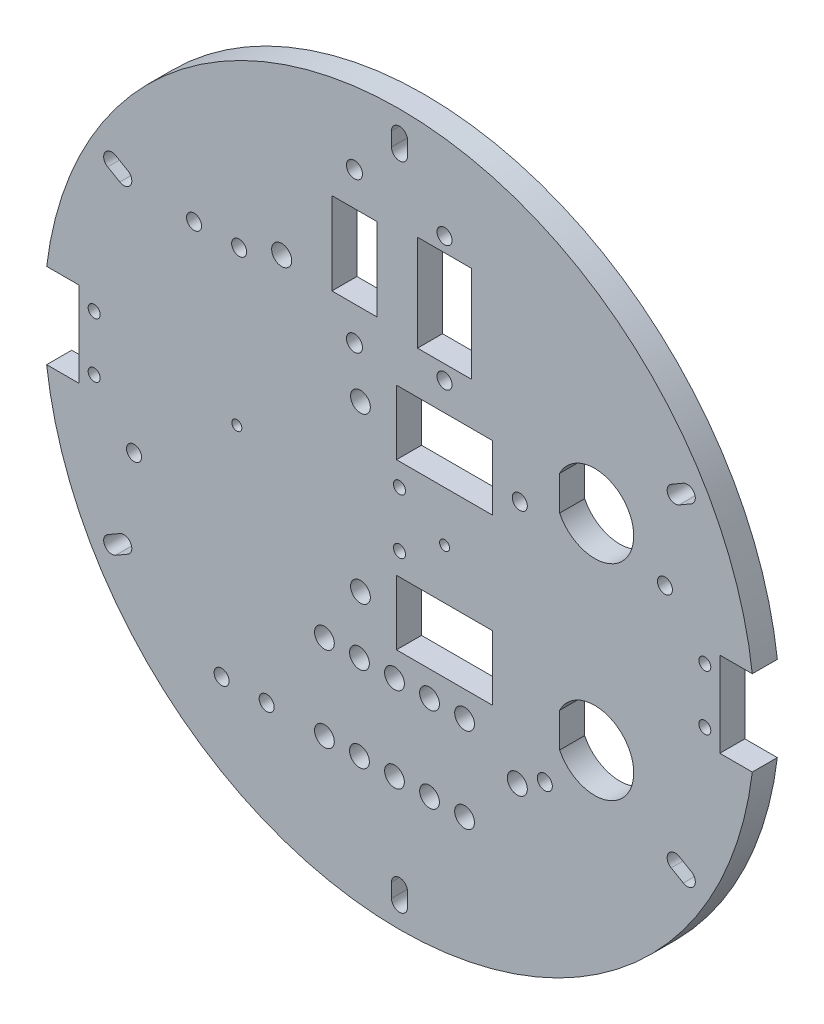
SolidWorks part; units mm, degrees
material "Alliage 1060"
ref_plane "Plan de face" through (0, 0, 0) normal (0, 0, 1) x (1, 0, 0)
ref_plane "Plan de dessus" through (0, 0, 0) normal (0, 1, 0) x (1, 0, 0)
ref_plane "Plan de droite" through (0, 0, 0) normal (1, 0, 0) x (0, 0, -1)
sketch "Esquisse1" plane through (0, 0, 0) normal (0, 0, 1) x (1, 0, 0)
  circle A0 centre (0, 0) radius 71
  dimension "D1" = 142
extrude "Boss.-Extru.1" add sketch "Esquisse1" along normal blind 5
sketch "Esquisse2" plane through (0, 0, 5) normal (0, 0, 1) x (1, 0, 0)
  line L0 (0, 0) -> (0, -76.1453) construction
  line L1 (97.9923, -8.5) -> (64, -8.5)
  line L2 (97.9923, -8.5) -> (97.9923, 8.5)
  line L3 (97.9923, 8.5) -> (64, 8.5)
  line L4 (64, -8.5) -> (64, 8.5)
  line L5 (0, 0) -> (103.2685, 0) construction
  line L7 (-85.8614, -8.5) -> (-64, -8.5)
  line L8 (-85.8614, -8.5) -> (-85.8614, 8.5)
  line L9 (-85.8614, 8.5) -> (-64, 8.5)
  line L10 (-64, -8.5) -> (-64, 8.5)
  dimension "D1" = 128
  dimension "D2" = 17
extrude "Enlèv. mat.-Extru.1" cut sketch "Esquisse2" against normal through all
hole_wizard "Dégagement M21" positions "Esquisse3" profile "Esquisse4" hole size "M2" standard "ISO" end condition through all
sketch "Esquisse3" plane through (0, 0, 0) normal (0, 0, -1) x (-1, 0, 0)
  line L0 (-64, 8.5) -> (-64, -8.5) construction
  line L1 (-64, 0) -> (-80.7851, 0) construction
  point P0 (-61, -5.5)
  dimension "D1" = 3
  dimension "D2" = 5.5
sketch "Esquisse4" plane through (61, -5.5, 0) normal (1, 0, 0) x (0, 1, 0)
  line L0 (0, 0) -> (0, 5)
  line L1 (0, 5) -> (1.2, 5)
  line L2 (1.2, 5) -> (1.2, 0)
  line L5 (1.2, 0) -> (0, 0)
  line L11 (0, -6.35) -> (0, 107.95) construction
  dimension "Diamètre du perçage jusqu'au prochain" = 2.4
  dimension "Profondeur du perçage jusqu'au prochain" = 5
pattern_linear "Répétition linéaire1" count 3 spacing 61 along (-1, 0, 0) count 2 spacing 11 along (0, 1, 0) of "Dégagement M21"
sketch "Esquisse7" plane through (0, 0, 0) normal (0, 0, -1) x (-1, 0, 0)
  line L1 (0, 0) -> (32.5, 0) construction
  circle A0 centre (32.5, 0) radius 1
  dimension "D2" = 2
  dimension "D4" = 32.5
extrude "Enlèv. mat.-Extru.2" cut sketch "Esquisse7" against normal blind 10
sketch "Esquisse8" plane through (0, 0, 5) normal (0, 0, 1) x (1, 0, 0)
  line L0 (32, 23.9409) -> (32, 17.0591)
  line L1 (64, 8.5) -> (64, -8.5) construction
  line L2 (70.4894, 8.5) -> (64, 8.5) construction
  line L3 (64, 0) -> (28.4808, 0) construction
  line L4 (32, -23.9409) -> (32, -17.0591)
  arc A0 (32, 23.9409) -> (32, 17.0591) centre (39, 20.5) cw
  arc A1 (32, -23.9409) -> (32, -17.0591) centre (39, -20.5) ccw
  point P5 (46.8, 20.5)
  dimension "D1" = 7.8
  dimension "D2" = 14.8
  dimension "D3" = 25
  dimension "D4" = 12
extrude "Enlèv. mat.-Extru.3" cut sketch "Esquisse8" against normal through all
hole_wizard "Dégagement M25" positions "Esquisse9" profile "Esquisse10" size "M2" standard "ISO" slot yes end condition through all
sketch "Esquisse9" plane through (0, 0, 5) normal (0, 0, 1) x (1, 0, 0)
  line L0 (0, 0) -> (56.2917, -32.5) construction
  line L2 (0, 0) -> (69.2789, 0) construction
  line L3 (53.6936, -31) -> (58.8897, -34) construction
  point P0 (56.2917, -32.5)
  dimension "D1" = 65
  dimension "D2" = 30
  dimension "D3" = 6
sketch "Esquisse10" plane through (56.2917, -32.5, 5) normal (1, 0, 0) x (0, -1, 0)
  line L0 (0, 0) -> (0, 5)
  line L1 (0, 5) -> (1.6, 5)
  line L2 (1.6, 5) -> (1.6, 0)
  line L5 (1.6, 0) -> (0, 0)
  line L11 (0, -6.35) -> (0, 107.95) construction
  dimension "Diamètre du perçage jusqu'au prochain" = 3.2
  dimension "Profondeur du perçage jusqu'au prochain" = 5
pattern_circular "Répétition circulaire1" count 6 over 360 about axis through (0, 0, 0) along (0, 0, 1) of "Dégagement M25"
sketch "Esquisse11" plane through (0, 0, 0) normal (0, 0, -1) x (-1, 0, 0)
  line L0 (0, 0) -> (-45.0649, 0) construction
  line L1 (-18.6, -10) -> (0.6, -10)
  line L2 (-18.6, -10) -> (-18.6, -22.9)
  line L3 (-18.6, -22.9) -> (0.6, -22.9)
  line L4 (0.6, -10) -> (0.6, -22.9)
  line L5 (0.6, 10) -> (0.6, 22.9)
  line L6 (-18.6, 22.9) -> (0.6, 22.9)
  line L7 (-18.6, 10) -> (-18.6, 22.9)
  line L8 (-18.6, 10) -> (0.6, 10)
  line L9 (22.5124, 41) -> (-32.2474, 41) construction
  line L10 (13.5, 32.75) -> (4.5, 32.75)
  line L11 (13.5, 32.75) -> (13.5, 49.25)
  line L12 (13.5, 49.25) -> (4.5, 49.25)
  line L13 (4.5, 32.75) -> (4.5, 49.25)
  line L14 (9, 56) -> (9, 26) construction
  line L15 (-9, 53.5) -> (-9, 28.5) construction
  line L16 (-18.6, 10) -> (0.6, -10) construction
  line L17 (-14.4, 50.6) -> (-3.6, 50.6)
  line L18 (-14.4, 50.6) -> (-14.4, 31.4)
  line L19 (-14.4, 31.4) -> (-3.6, 31.4)
  line L20 (-3.6, 50.6) -> (-3.6, 31.4)
  line L21 (0.6, 10) -> (-18.6, -10) construction
  circle A0 centre (9, 26) radius 1.6
  circle A1 centre (9, 56) radius 1.6
  circle A2 centre (-9, 28.5) radius 1.5
  circle A3 centre (-9, 53.5) radius 1.5
  circle A4 centre (7.8, 16.45) radius 1.975
  circle A5 centre (7.8, -16.45) radius 1.975
  circle A6 centre (-9, 0) radius 1
  point P27 (4.5, 41)
  point P28 (13.5, 41)
  dimension "D5" = 3.2
  dimension "D6" = 30
  dimension "D9" = 41
  dimension "D10" = 3
  dimension "D16" = 3.95
  dimension "D19" = 2
  dimension "D1" = 19.2
  dimension "D2" = 12.9
  dimension "D3" = 10
  dimension "D4" = 7.8
  dimension "D7" = 9
  dimension "D8" = 25
  dimension "D11" = 16.5
  dimension "D12" = 9
  dimension "D13" = 10.8
  dimension "D14" = 19.2
  dimension "D15" = 9
  dimension "D17" = 6.45
extrude "Enlèv. mat.-Extru.4" cut sketch "Esquisse11" against normal through all
sketch "Esquisse12" plane through (0, 0, 5) normal (0, 0, 1) x (1, 0, 0)
  circle A0 centre (-15, -45) radius 1.975
  dimension "D1" = 3.95
  dimension "D2" = 45
  dimension "D3" = 15
extrude "Enlèv. mat.-Extru.5" cut sketch "Esquisse12" against normal through all
pattern_linear "Répétition linéaire3" count 5 spacing 7 along (1, 0, 0) count 2 spacing 17 along (0, 1, 0) of "Enlèv. mat.-Extru.5"
sketch "Esquisse13" plane through (0, 0, 0) normal (0, 0, -1) x (-1, 0, 0)
  circle A0 centre (23.5374, 33.9599) radius 2
  dimension "D1" = 4
  dimension "D2" = 23.5374
  dimension "D3" = 33.9599
extrude "Enlèv. mat.-Extru.6" cut sketch "Esquisse13" against normal through all
pattern_circular "Répétition circulaire2" count 2 over 360 about axis through (0, 0, 5) along (0, 0, 1) of "Enlèv. mat.-Extru.6" reverse direction yes
sketch "Esquisse15" plane through (0, 0, 5) normal (0, 0, 1) x (1, 0, 0)
  circle A0 centre (53.035, 15.0401) radius 1.5
  circle A1 centre (24.035, 15.0401) radius 1.5
  circle A2 centre (29.035, -30.9599) radius 1.5
  circle A3 centre (-35.5374, -45.0401) radius 1.5
  circle A4 centre (-26.5374, -45.0401) radius 1.5
  circle A5 centre (-41.0374, 30.9599) radius 1.5
  circle A6 centre (-32.0374, 30.9599) radius 1.5
  circle A7 centre (-53.0374, -15.0401) radius 1.5
  dimension "D1" = 3
  dimension "D2" = 3
  dimension "D3" = 3
  dimension "D4" = 3
  dimension "D5" = 3
  dimension "D6" = 3
  dimension "D7" = 3
  dimension "D8" = 3
  dimension "D9" = 53.0374
  dimension "D10" = 15.0401
  dimension "D11" = 45.0401
  dimension "D12" = 35.5374
  dimension "D13" = 26.5374
  dimension "D14" = 45.0401
  dimension "D15" = 29.035
  dimension "D16" = 30.9599
  dimension "D17" = 24.035
  dimension "D18" = 15.0401
  dimension "D19" = 15.0401
  dimension "D20" = 53.035
  dimension "D21" = 32.0374
  dimension "D22" = 30.9599
  dimension "D23" = 30.9599
  dimension "D24" = 41.0374
extrude "Enlèv. mat.-Extru.8" cut sketch "Esquisse15" against normal blind 10
